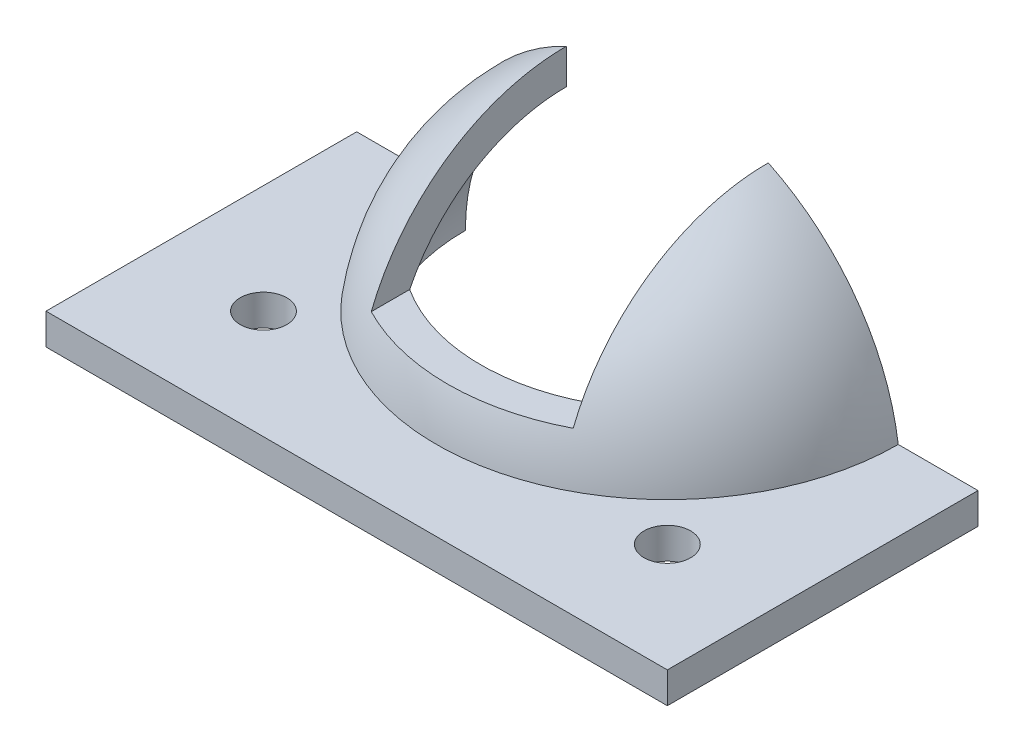
SolidWorks part; units mm, degrees
ref_plane "Front Plane" through (0, 0, 0) normal (0, 0, 1) x (1, 0, 0)
ref_plane "Top Plane" through (0, 0, 0) normal (0, 1, 0) x (1, 0, 0)
ref_plane "Right Plane" through (0, 0, 0) normal (1, 0, 0) x (0, 0, -1)
sketch "Sketch1" plane through (0, 0, 0) normal (0, 0, 1) x (1, 0, 0)
  line L0 (16.51, 0) -> (19.05, 0) construction
  line L1 (19.05, 0) -> (16.51, 0) construction
  line L2 (19.05, 0) -> (16.51, 0)
  line L3 (0, 19.05) -> (0, 16.51)
  arc A0 (19.05, 0) -> (0, 19.05) centre (0, 0) ccw
  arc A2 (16.51, 0) -> (0, 16.51) centre (0, 0) ccw
  circle A3 centre (0, 0) radius 19.05 construction
  circle A4 centre (0, 0) radius 16.51 construction
  dimension "D1" = 38.1
  dimension "D2" = 2.54
revolve "Revolve1" add sketch "Sketch1" angle 360 about L3
sketch "Sketch2" plane through (0, 0, 0) normal (0, 0, 1) x (1, 0, 0)
  line L0 (0, 6.35) -> (0, 0) construction
  line L1 (-8.255, 22.7688) -> (8.255, 22.7688)
  line L2 (-8.255, 22.7688) -> (-8.255, 6.35)
  line L3 (-8.255, 6.35) -> (8.255, 6.35)
  line L4 (8.255, 22.7688) -> (8.255, 6.35)
  dimension "D1" = 6.35
  dimension "D2" = 16.51
extrude "Cut-Extrude1" cut sketch "Sketch2" against normal mid plane 127
sketch "Sketch3" plane through (0, 0, 0) normal (0, -1, 0) x (1, 0, 0)
  line L1 (25.4, -25.4) -> (-25.4, -25.4)
  line L2 (25.4, -25.4) -> (25.4, 25.4)
  line L3 (25.4, 25.4) -> (-25.4, 25.4)
  line L4 (-25.4, -25.4) -> (-25.4, 25.4)
  line L5 (25.4, -25.4) -> (-25.4, 25.4) construction
  line L6 (25.4, 25.4) -> (-25.4, -25.4) construction
  circle A0 centre (0, 0) radius 16.51
  point P0 (0, 0)
  dimension "D2" = 33.02
  dimension "D1" = 50.8
sketch "Sketch4" plane through (0, 0, 0) normal (0, -1, 0) x (1, 0, 0)
  line L0 (25.4, -25.4) -> (-25.4, 25.4) construction
  circle A0 centre (0.1236, -0.1236) radius 16.51
  dimension "D1" = 33.02
extrude "Boss-Extrude1" add sketch "Sketch3" against normal blind 2.54
sketch "Sketch5" plane through (0, 2.54, 0) normal (0, 1, 0) x (1, 0, 0)
  line L0 (-16.51, 25.4) -> (-16.51, 16.51) construction
  line L1 (-25.4, 25.4) -> (25.4, 25.4) construction
  line L2 (-16.51, 16.51) -> (-25.4, 16.51) construction
  line L3 (-25.4, -25.4) -> (-25.4, 25.4) construction
  circle A0 centre (-16.51, 16.51) radius 1.905
  dimension "D2" = 3.81
  dimension "D1" = 8.89
extrude "Cut-Extrude3" cut sketch "Sketch5" against normal through all contours A0
pattern_linear "LPattern1" count 2 spacing 33.02 along (1, 0, 0) count 2 spacing 33.02 along (0, 0, 1) of "Cut-Extrude3"
sketch "Sketch6" plane through (0, 0, 0) normal (0, 0, 1) x (1, 0, 0)
  line L1 (-27.8436, 17.9221) -> (28.4379, 17.9221)
  line L2 (-27.8436, 17.9221) -> (-27.8436, -2.225)
  line L3 (-27.8436, -2.225) -> (28.4379, -2.225)
  line L4 (28.4379, 17.9221) -> (28.4379, -2.225)
extrude "Cut-Extrude4" cut sketch "Sketch6" against normal through all contours L2 L3 L4 L1
